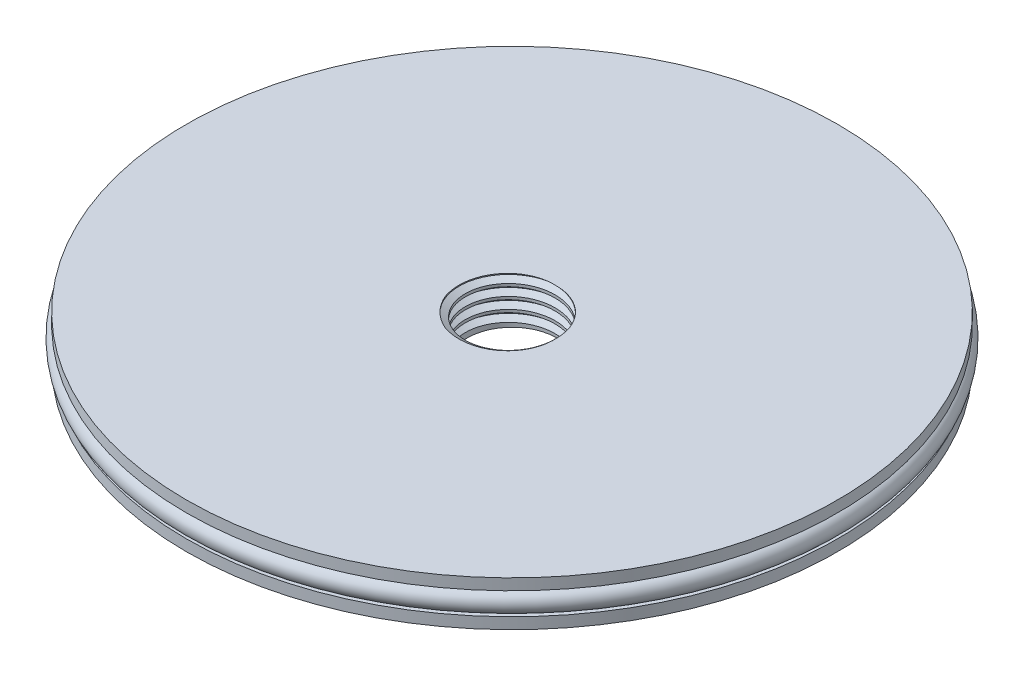
SolidWorks part; units mm, degrees
ref_plane "Front Plane" through (0, 0, 0) normal (0, 0, 1) x (1, 0, 0)
ref_plane "Top Plane" through (0, 0, 0) normal (0, 1, 0) x (1, 0, 0)
ref_plane "Right Plane" through (0, 0, 0) normal (1, 0, 0) x (0, 0, -1)
sketch "Sketch2" plane through (0, 0, 0) normal (0, 0, 1) x (1, 0, 0)
  line L1 (0, 0) -> (-72.5, 0)
  line L2 (0, 0) -> (0, 10)
  line L3 (0, 10) -> (-72.5, 10)
  line L4 (-72.5, 0) -> (-72.5, 10) construction
  line L8 (-72.5, 10) -> (-72.5, 7.5)
  line L9 (-72.5, 0) -> (-72.5, 2.5)
  line L11 (-72.5, 7.5) -> (-68.5, 7.5)
  line L13 (-72.5, 2.5) -> (-68.5, 2.5)
  line L14 (-68.5, 7.5) -> (-68.5, 2.5)
  point P6 (-70, 5)
  dimension "D1" = 72.5
  dimension "D2" = 10
  dimension "D3" = 5
  dimension "D4" = 4
revolve "Revolve1" add sketch "Sketch2" angle 360 about L2
sketch "Sketch4" plane through (0, 0, 0) normal (0, 0, 1) x (1, 0, 0)
  line L0 (-72.5, 10) -> (-72.5, 7.5) construction
  circle A0 centre (-71, 5) radius 2.5 construction
  circle A1 centre (-71, 5) radius 2.4
  dimension "D1" = 1.5
  dimension "D2" = 4.8
revolve "Revolve2" add sketch "Sketch4" angle 360 about L2
sketch "Sketch9" plane through (0, 10, 0) normal (0, 1, 0) x (1, 0, 0)
  circle A0 centre (0, 0) radius 10
extrude "Cut-Extrude2" cut sketch "Sketch9" against normal blind 10
thread "Thread1" pitch 2.5 method cut profile "Thread Profile1" start angle 0, offset 0, length 10, pitch 2.5, diameter 20
ref_plane "Plane1" through (10, 0, 0) normal (0, 0, 1) x (1, 0, 0)
sketch "Thread Profile1" plane through (10, 0, 0) normal (0, 0, 1) x (1, 0, 0)
  line L0 (0, 0) -> (0, 2.5) construction
  line L1 (0, 0) -> (1.3532, 0.7812)
  line L2 (1.3532, 0.7812) -> (1.3532, 1.0937)
  line L3 (1.3532, 1.0937) -> (0, 1.875)
  line L4 (1.3532, 0.9375) -> (0, 0.9375) construction
  line L11 (0, 0) -> (0, 1.875)
  point P2 (0, 0)
  dimension "Pitch" = 2.5
  dimension "Profile_Angle" = 60
  dimension "Profile_Land" = 0.3125
  dimension "Profile_Height" = 1.3532
